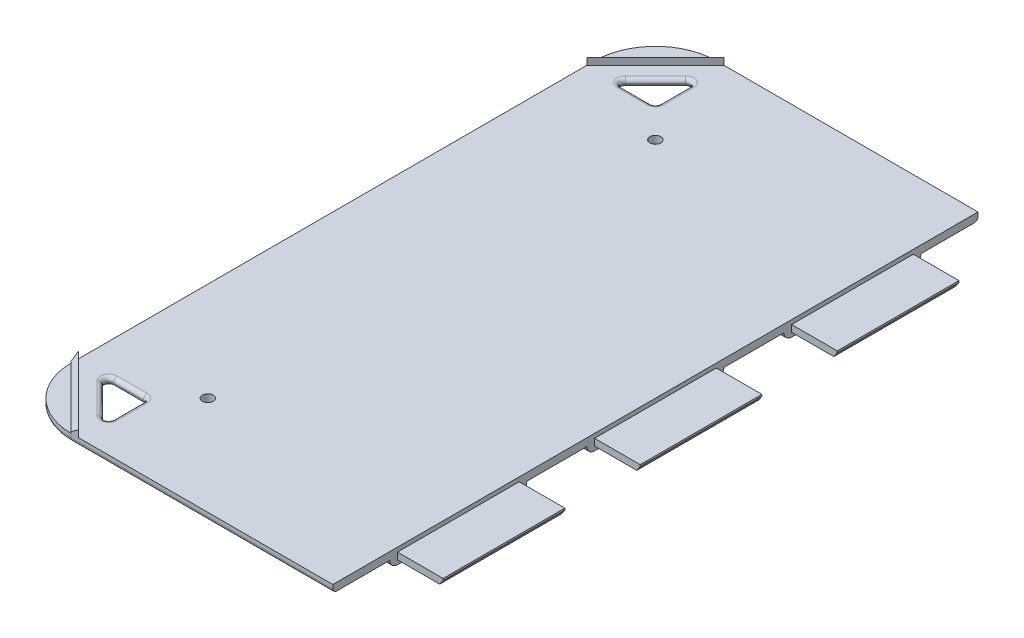
SolidWorks part; units mm, degrees
ref_plane "Front Plane" through (0, 0, 0) normal (0, 0, 1) x (1, 0, 0)
ref_plane "Top Plane" through (0, 0, 0) normal (0, 1, 0) x (1, 0, 0)
ref_plane "Right Plane" through (0, 0, 0) normal (1, 0, 0) x (0, 0, -1)
sketch "Sketch1" plane through (0, 0, 0) normal (0, 1, 0) x (1, 0, 0)
  line L0 (0, -134.62) -> (0, 134.62)
  line L1 (-134.62, -134.62) -> (134.62, -134.62)
  line L2 (-134.62, -134.62) -> (-134.62, 134.62)
  line L3 (-134.62, 134.62) -> (134.62, 134.62)
  line L4 (134.62, -134.62) -> (134.62, 134.62)
  line L5 (-134.62, -134.62) -> (134.62, 134.62) construction
  line L6 (-134.62, 134.62) -> (134.62, -134.62) construction
  point P0 (0, 0)
  point P9 (0, 0)
  dimension "D1" = 269.24
extrude "Boss-Extrude1" add sketch "Sketch1" along normal blind 3.175 contours L3 L2 L1 L0 region at (-67.31, 0, 0)
sketch "Sketch2" plane through (0, 3.175, 0) normal (0, 1, 0) x (1, 0, 0)
  line L0 (-109.22, -134.62) -> (-134.62, -109.22)
  line L1 (-109.22, -134.62) -> (-106.045, -134.62)
  line L2 (-106.045, -134.62) -> (-134.62, -106.045)
  line L3 (-134.62, -106.045) -> (-134.62, -109.22)
  line L4 (0, 134.62) -> (-134.62, 134.62)
  line L5 (-134.62, 134.62) -> (-134.62, -134.62)
  line L6 (-134.62, -134.62) -> (0, -134.62)
  line L7 (0, -134.62) -> (0, 134.62)
  line L8 (0, 134.62) -> (-134.62, 134.62)
  line L9 (-134.62, 134.62) -> (-134.62, -134.62)
  line L10 (-134.62, -134.62) -> (0, -134.62)
  line L11 (0, -134.62) -> (0, 134.62)
  line L12 (-109.22, 134.62) -> (-134.62, 109.22)
  line L13 (-134.62, 109.22) -> (-134.62, 106.045)
  line L14 (-134.62, 106.045) -> (-106.045, 134.62)
  line L15 (-106.045, 134.62) -> (-109.22, 134.62)
  line L16 (-120.3325, 120.3325) -> (-115.3934, 115.3934)
  line L17 (-120.3325, -120.3325) -> (-115.3934, -115.3934)
  line L18 (-124.9184, -105.8684) -> (-105.8684, -124.9184)
  line L19 (-105.8684, -124.9184) -> (-105.8684, -105.8684)
  line L20 (-105.8684, -105.8684) -> (-124.9184, -105.8684)
  line L21 (-124.9184, 105.8684) -> (-105.8684, 124.9184)
  line L22 (-105.8684, 124.9184) -> (-105.8684, 105.8684)
  line L23 (-105.8684, 105.8684) -> (-124.9184, 105.8684)
  line L24 (-120.3325, 120.3325) -> (-93.3917, 93.3917)
  line L25 (-120.3325, -120.3325) -> (-93.3917, -93.3917)
  circle A0 centre (-93.3917, 93.3917) radius 2.286
  circle A1 centre (-93.3917, -93.3917) radius 2.286
  point P12 (-120.3325, -120.3325)
  point P14 (-120.3325, 120.3325)
  point P21 (-115.3934, -115.3934)
  point P25 (-115.3934, 115.3934)
  line M24 (-134.62, 134.62) -> (-134.62, -134.62)
  line M25 (-134.62, -134.62) -> (0, -134.62)
  dimension "D17" = 4.572
  dimension "D2" = 25.4
  dimension "D3" = 25.4
  dimension "D4" = 3.175
  dimension "D5" = 25.4
  dimension "D6" = 3.175
  dimension "D7" = 25.4
  dimension "D8" = 3.175
  dimension "D9" = 6.985
  dimension "D10" = 6.985
  dimension "D11" = 90
  dimension "D12" = 90
  dimension "D13" = 19.05
  dimension "D14" = 90
  dimension "D15" = 19.05
  dimension "D16" = 38.1
  dimension "D18" = 90
  dimension "D19" = 90
  dimension "D1" = 0
extrude "Boss-Extrude2" add sketch "Sketch2" along normal blind 3.175 contours L9 L14 L8 L12 | L2 L0 M25 M24 region at (-121.1107, 3.175, 121.1107) region at (-121.1107, 3.175, -121.1107)
extrude "Cut-Extrude1" cut sketch "Sketch2<3>" against normal up to next contours L23 L21 L22 | L19 L20 L18 | A1 | A0
sketch "Sketch2<3>" plane through (0, 3.175, 0) normal (0, 1, 0) x (1, 0, 0) same geometry as "Sketch2"
chamfer "Chamfer1" distance 2.54 2 edges at (-121.92, 6.35, -121.92) (-121.92, 6.35, 121.92)
fillet "Fillet1" radius 1.905 6 edges at (-105.8684, 1.5875, -105.8684) (-124.9184, 1.5875, -105.8684) (-105.8684, 1.5875, -124.9184) (-105.8684, 1.5875, 124.9184) (-105.8684, 1.5875, 105.8684) (-124.9184, 1.5875, 105.8684)
fillet "Fillet2" radius 1.5875 24 edges at (-107.0443, 0, 122.0793) (-105.8684, 0, 114.0463) (-106.4263, 0, 106.4263) (-114.0463, 0, 105.8684) (-122.0793, 0, 107.0443) (-122.0793, 3.175, 107.0443) (-114.0463, 3.175, 105.8684) (-106.4263, 3.175, 106.4263) (-105.8684, 3.175, 114.0463) (-107.0443, 3.175, 122.0793) (-122.0793, 3.175, -107.0443) (-114.0463, 3.175, -105.8684) (-106.4263, 3.175, -106.4263) (-105.8684, 3.175, -114.0463) (-107.0443, 3.175, -122.0793) (-107.0443, 0, -122.0793) (-105.8684, 0, -114.0463) (-106.4263, 0, -106.4263) (-114.0463, 0, -105.8684) (-122.0793, 0, -107.0443) (-115.3934, 0, 115.3934) (-115.3934, 3.175, 115.3934) (-115.3934, 3.175, -115.3934) (-115.3934, 0, -115.3934)
fillet "Fillet3" radius 25.4 2 edges at (-134.62, 1.5875, 134.62) (-134.62, 1.5875, -134.62)
fillet "Fillet4" radius 1.5875 5 edges at (-127.1805, 0, -127.1805) (-54.61, 0, -134.62) (-134.62, 0, 0) (-127.1805, 0, 127.1805) (-54.61, 0, 134.62)
sketch "Sketch3" plane through (0, 0, 0) normal (0, -1, 0) x (1, 0, 0)
  line L1 (0, 28.575) -> (-31.75, 28.575)
  line L2 (0, 28.575) -> (0, -28.575)
  line L3 (0, -28.575) -> (-31.75, -28.575)
  line L4 (-109.22, -133.0325) -> (0, -133.0325)
  line L5 (0, -133.0325) -> (0, 133.0325)
  line L6 (0, 133.0325) -> (-109.22, 133.0325)
  line L7 (-133.0325, 109.22) -> (-133.0325, -109.22)
  line L8 (-109.22, -133.0325) -> (0, -133.0325)
  line L9 (0, -133.0325) -> (0, 133.0325)
  line L10 (0, 133.0325) -> (-109.22, 133.0325)
  line L11 (-133.0325, 109.22) -> (-133.0325, -109.22)
  line L12 (-31.75, 28.575) -> (-31.75, -28.575)
  line L13 (-31.75, 110.8075) -> (0, 110.8075)
  line L14 (-31.75, 110.8075) -> (-31.75, 53.6575)
  line L15 (-31.75, 53.6575) -> (0, 53.6575)
  line L16 (0, 110.8075) -> (0, 53.6575)
  line L17 (-31.75, -53.6575) -> (0, -53.6575)
  line L18 (-31.75, -53.6575) -> (-31.75, -110.8075)
  line L19 (-31.75, -110.8075) -> (0, -110.8075)
  line L20 (0, -53.6575) -> (0, -110.8075)
  arc A2 (-133.0325, -109.22) -> (-109.22, -133.0325) centre (-109.22, -109.22) ccw
  arc A3 (-109.22, 133.0325) -> (-133.0325, 109.22) centre (-109.22, 109.22) ccw
  arc A4 (-133.0325, -109.22) -> (-109.22, -133.0325) centre (-109.22, -109.22) ccw
  arc A5 (-109.22, 133.0325) -> (-133.0325, 109.22) centre (-109.22, 109.22) ccw
  point P12 (0, 0)
  point P22 (-31.75, -82.2325)
  point P23 (-31.75, 82.2325)
  line M33 (0, -133.0325) -> (0, 133.0325)
  dimension "D2" = 57.15
  dimension "D3" = 31.75
  dimension "D4" = 50.8
  dimension "D5" = 50.8
  dimension "D1" = 0
extrude "Boss-Extrude3" add sketch "Sketch3" along normal blind 3.175 contours L14 L15 L9 L13 | L1 L12 L3 M33 | L18 L19 L9 L17 region at (-15.875, 0, 0) region at (-15.875, 0, 82.2325) region at (-15.875, 0, -82.2325)
sketch "Sketch4" plane through (0, 0, 0) normal (1, 0, 0) x (0, 0, -1)
  line L0 (-110.8075, 0) -> (-110.8075, 3.175)
  line L1 (-53.6575, 0) -> (-53.6575, 3.175)
  line L2 (-28.575, 0) -> (-28.575, 3.175)
  line L3 (28.575, 0) -> (28.575, 3.175)
  line L4 (53.6575, 0) -> (53.6575, 3.175)
  line L5 (110.8075, 0) -> (110.8075, 3.175)
  line L6 (28.575, 3.175) -> (-28.575, 3.175)
  line L7 (-53.6575, 3.175) -> (-110.8075, 3.175)
  line L9 (107.6325, -1.397) -> (56.8325, -1.397)
  line L10 (107.6325, -1.397) -> (107.6325, 1.397)
  line L11 (107.6325, 1.397) -> (56.8325, 1.397)
  line L12 (56.8325, -1.397) -> (56.8325, 1.397)
  line L13 (107.6325, -1.397) -> (56.8325, 1.397) construction
  line L14 (107.6325, 1.397) -> (56.8325, -1.397) construction
  line L15 (25.4, -1.397) -> (-25.4, -1.397)
  line L16 (-133.0325, 0) -> (-110.8075, 0)
  line L17 (-110.8075, 0) -> (-110.8075, -3.175)
  line L18 (-110.8075, -3.175) -> (-53.6575, -3.175)
  line L19 (-53.6575, -3.175) -> (-53.6575, 0)
  line L20 (-53.6575, 0) -> (-28.575, 0)
  line L21 (-28.575, 0) -> (-28.575, -3.175)
  line L22 (-28.575, -3.175) -> (28.575, -3.175)
  line L23 (28.575, -3.175) -> (28.575, 0)
  line L24 (28.575, 0) -> (53.6575, 0)
  line L25 (53.6575, 0) -> (53.6575, -3.175)
  line L26 (53.6575, -3.175) -> (110.8075, -3.175)
  line L27 (110.8075, -3.175) -> (110.8075, 0)
  line L28 (110.8075, 0) -> (133.0325, 0)
  line L29 (134.62, 1.5875) -> (134.62, 3.175)
  line L30 (134.62, 3.175) -> (-134.62, 3.175)
  line L31 (-134.62, 3.175) -> (-134.62, 1.5875)
  line L33 (-110.8075, 0) -> (-110.8075, -3.175)
  line L34 (-110.8075, -3.175) -> (-53.6575, -3.175)
  line L35 (-53.6575, -3.175) -> (-53.6575, 0)
  line L37 (-28.575, 0) -> (-28.575, -3.175)
  line L38 (-28.575, -3.175) -> (28.575, -3.175)
  line L39 (28.575, -3.175) -> (28.575, 0)
  line L41 (53.6575, 0) -> (53.6575, -3.175)
  line L42 (53.6575, -3.175) -> (110.8075, -3.175)
  line L43 (110.8075, -3.175) -> (110.8075, 0)
  line L46 (110.8075, 3.175) -> (53.6575, 3.175)
  line L48 (25.4, -1.397) -> (25.4, 1.397)
  line L49 (25.4, 1.397) -> (-25.4, 1.397)
  line L50 (-25.4, -1.397) -> (-25.4, 1.397)
  line L51 (25.4, -1.397) -> (-25.4, 1.397) construction
  line L52 (25.4, 1.397) -> (-25.4, -1.397) construction
  line L53 (-56.8325, -1.397) -> (-107.6325, -1.397)
  line L54 (-56.8325, -1.397) -> (-56.8325, 1.397)
  line L55 (-56.8325, 1.397) -> (-107.6325, 1.397)
  line L56 (-107.6325, -1.397) -> (-107.6325, 1.397)
  line L57 (-56.8325, -1.397) -> (-107.6325, 1.397) construction
  line L58 (-56.8325, 1.397) -> (-107.6325, -1.397) construction
  arc A2 (133.0325, 0) -> (134.62, 1.5875) centre (133.0325, 1.5875) ccw
  arc A3 (-134.62, 1.5875) -> (-133.0325, 0) centre (-133.0325, 1.5875) ccw
  point P10 (-82.2325, -3.175)
  point P20 (0, -3.175)
  point P22 (82.2325, -3.175)
  point P24 (82.2325, 0)
  point P33 (0, 0)
  point P40 (-82.2325, 0)
  point P45 (0, 0)
  point P46 (0, 0)
  point P47 (0, 0)
  dimension "D2" = 2.794
  dimension "D3" = 50.8
  dimension "D1" = 0
extrude "Boss-Extrude4" add sketch "Sketch4" along normal blind 19.05 contours L56 L53 L54 L55 | L50 L15 L48 L49 | L12 L9 L10 L11 region at (0, 0, -82.2325) region at (0, 0, 0) region at (0, 0, 82.2325)
fillet "Fillet5" radius 12.7 6 edges at (-31.75, -1.5875, 53.6575) (-31.75, -1.5875, 110.8075) (-31.75, -1.5875, 28.575) (-31.75, -1.5875, -28.575) (-31.75, -1.5875, -53.6575) (-31.75, -1.5875, -110.8075)
fillet "Fillet6" radius 3.175 15 edges at (-9.525, -3.175, -53.6575) (-28.0303, -3.175, -57.3772) (-31.75, -3.175, -82.2325) (-28.0303, -3.175, -107.0878) (-9.525, -3.175, 28.575) (-28.0303, -3.175, 24.8553) (-31.75, -3.175, 0) (-28.0303, -3.175, -24.8553) (-9.525, -3.175, 110.8075) (-28.0303, -3.175, 107.0878) (-31.75, -3.175, 82.2325) (-28.0303, -3.175, 57.3772) (-9.525, -3.175, -110.8075) (-9.525, -3.175, -28.575) (-9.525, -3.175, 53.6575)
chamfer "Chamfer2" distance 2.032 angle 35 3 edges at (19.05, -1.397, -82.2325) (19.05, -1.397, 0) (19.05, -1.397, 82.2325) first distance on face at (19.05, 0, -82.2325) first distance on face at (19.05, 0, 0) first distance on face at (19.05, 0, 82.2325)
